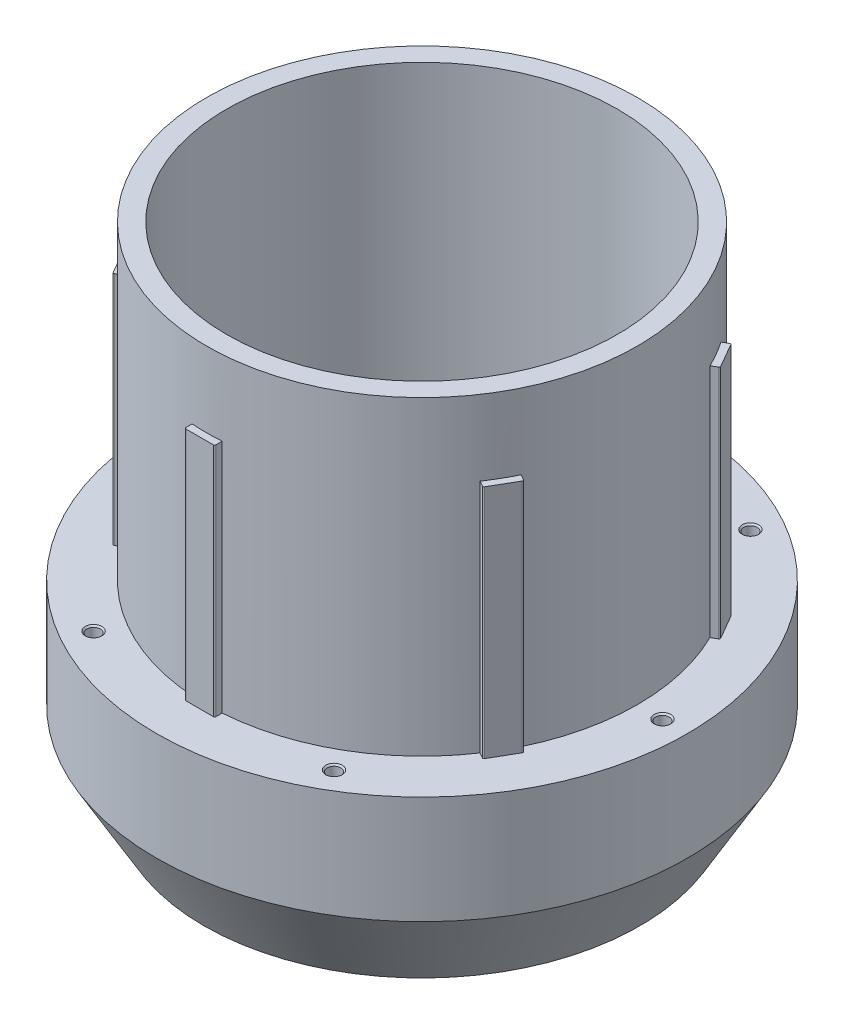
SolidWorks part; units mm, degrees
material "PET"
ref_plane "Front Plane" through (0, 0, 0) normal (0, 0, 1) x (1, 0, 0)
ref_plane "Top Plane" through (0, 0, 0) normal (0, 1, 0) x (1, 0, 0)
ref_plane "Right Plane" through (0, 0, 0) normal (1, 0, 0) x (0, 0, -1)
sketch "Sketch1" plane through (0, 0, 0) normal (0, 0, 1) x (1, 0, 0)
  line L0 (40.5, -30) -> (43.5, -30)
  line L1 (43.5, -30) -> (53, -13.5455)
  line L2 (53, -13.5455) -> (53, 8)
  line L3 (53, 8) -> (43, 8)
  line L4 (43, 8) -> (43, 70)
  line L5 (43, 70) -> (39, 70)
  line L6 (39, 70) -> (39, 0)
  line L7 (39, 0) -> (40.5, 0)
  line L8 (40.5, 0) -> (40.5, -30)
  line L9 (0, 0) -> (0, 32.7449) construction
  dimension "D1" = 8
  dimension "D2" = 40.5
  dimension "D3" = 3
  dimension "D6" = 30
  dimension "D7" = 43
  dimension "D8" = 70
  dimension "D9" = 39
  dimension "D5" = 53
  dimension "D4" = 30
revolve "body" add sketch "Sketch1" angle 360 about L9
sketch "Sketch2" plane through (0, 8, 0) normal (0, 1, 0) x (1, 0, 0)
  point P0 (48, 0)
  dimension "D1" = 48
hole_wizard "spring_screw_hole" positions "Sketch2" profile "Sketch3" hole size "Ø2.7" standard "DIN"
sketch "Sketch3" plane through (48, 8, 0) normal (1, 0, 0) x (0, 0, 1)
  line L0 (0, 0) -> (0, 20.8112)
  line L1 (0, 20.8112) -> (1.35, 20)
  line L2 (1.35, 20) -> (1.35, 0.3)
  line L3 (1.35, 0.3) -> (1.65, 0)
  line L5 (1.65, 0) -> (0, 0)
  line L6 (-1.35, 0.3) -> (-1.65, 0) construction
  line L10 (0, 20.8112) -> (-1.35, 20) construction
  line L11 (0, -6.35) -> (0, 107.95) construction
  dimension "Hole Dia." = 2.7
  dimension "Hole Depth" = 20
  dimension "Near C'Sink Dia." = 3.3
  dimension "Near C'Sink Angle" = 90
  dimension "Drill Angle" = 118
sketch "Sketch4" plane through (0, 8, 0) normal (0, 1, 0) x (1, 0, 0)
  line L0 (35.6486, 24.0453) -> (38.6481, 18.85)
  line L1 (38.6481, 18.85) -> (39.9472, 19.6)
  line L2 (39.9472, 19.6) -> (36.9477, 24.7953)
  line L3 (36.9477, 24.7953) -> (35.6486, 24.0453)
  line L4 (0, 0) -> (35.6486, 24.0453) construction
  line L5 (0, 0) -> (38.6481, 18.85) construction
  line L6 (0, 0) -> (48, 0) construction
  circle A0 centre (0, 0) radius 43 construction
  dimension "D1" = 26
  dimension "D2" = 8
  dimension "D3" = 1.5
extrude "driving_extrusion" add sketch "Sketch4" along normal blind 47
fillet "driving_extrusion_fillets" radius 0.25 2 edges at (36.9477, 31.5, -24.7953) (39.9472, 31.5, -19.6)
pattern_circular "main_pattern" count 6 over 360 about axis through (0, 8, 0) along (0, -1, 0) of "spring_screw_hole", "driving_extrusion", "driving_extrusion_fillets"
equation "\"paper_size\" = 600mm"
equation "\"cb_roll_d_outer\" = 80mm"
equation "\"cb_roll_d_inner\" = 78mm"
equation "\"helper_d\" = 86mm"
equation "\"outer_d\" = 106mm"
equation "\"spring_l_max\" = 25mm"
equation "\"spring_l_min\" = 10mm"
equation "\"D2@Sketch1\"=(\"cb_roll_d_outer\" + 1) / 2"
equation "\"D7@Sketch1\"= \"helper_d\" / 2"
equation "\"D9@Sketch1\"=\"cb_roll_d_inner\"  / 2"
equation "\"D5@Sketch1\"=\"outer_d\" / 2"
equation "\"attached_len\" = 70mm"
equation "\"D8@Sketch1\"=\"attached_len\""
equation "\"D1@Sketch2\"=(\"outer_d\" + \"helper_d\") / 4"
equation "\"D1@driving_extrusion\" = \"attached_len\" - \"spring_l_max\" + \"spring_l_min\" - 8"
